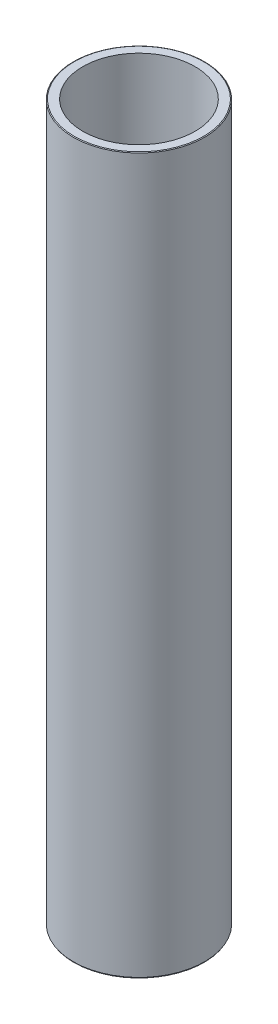
SolidWorks part; units mm, degrees
ref_plane "Front Plane" through (0, 0, 0) normal (0, 0, 1) x (1, 0, 0)
ref_plane "Top Plane" through (0, 0, 0) normal (0, 1, 0) x (1, 0, 0)
ref_plane "Right Plane" through (0, 0, 0) normal (1, 0, 0) x (0, 0, -1)
sketch "Sketch1" plane through (0, 0, 0) normal (0, 1, 0) x (1, 0, 0)
  circle A0 centre (0, 0) radius 55
  dimension "SHAFT_OD" = 110
extrude "Boss-Extrude1" add sketch "Sketch1" along normal blind 600
sketch "Sketch2" plane through (0, 0, 0) normal (0, 1, 0) x (1, 0, 0)
  circle A0 centre (0, 0) radius 47.09
  dimension "BORE_D" = 94.18
extrude "Cut-Extrude1" cut sketch "Sketch2" along normal through all
chamfer "Chamfer1" distance 0.4147 angle 60 2 edges at (0, 600, 55) (0, 0, 55) first distance on face at (0, 600, 55) first distance on face at (0, 0, 47.09)
